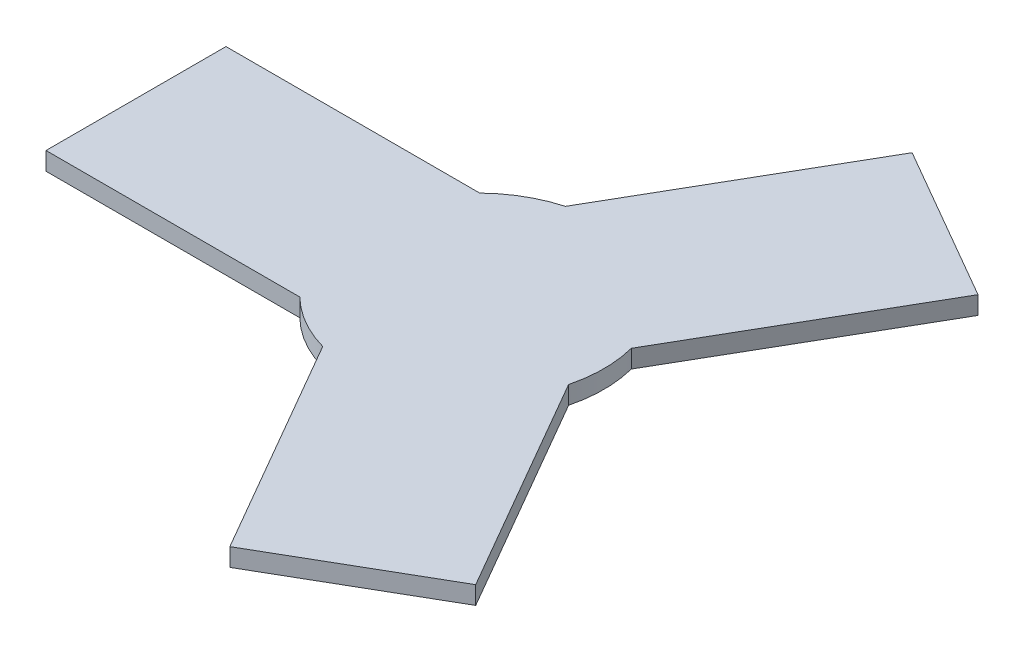
SolidWorks part; units mm, degrees
ref_plane "Plan de face" through (0, 0, 0) normal (0, 0, 1) x (1, 0, 0)
ref_plane "Plan de dessus" through (0, 0, 0) normal (0, 1, 0) x (1, 0, 0)
ref_plane "Plan de droite" through (0, 0, 0) normal (1, 0, 0) x (0, 0, -1)
sketch "Esquisse3" plane through (0, 0, 0) normal (0, 1, 0) x (1, 0, 0)
  line L0 (-150.1573, 0) -> (189.6273, 0) construction
  line L1 (-83.8395, -145.9242) -> (87.7229, 151.2306) construction
  line L2 (-78.0725, 135.2255) -> (117.7517, -203.9519) construction
  line L3 (-125, 131.2995) -> (-125, -153.5705) construction
  line L4 (-10.0538, -25) -> (-95, -25)
  line L5 (-10.0538, -25) -> (-10.0538, 25)
  line L6 (-10.0538, 25) -> (-14.4338, 25)
  line L7 (-95, -25) -> (-95, 25)
  line L8 (-10.0538, -25) -> (-95, 25) construction
  line L9 (-10.0538, 25) -> (-95, -25) construction
  line L10 (-24.4949, 25) -> (-95, 25)
  line L11 (33.8981, 8.7132) -> (69.1506, 69.7724)
  line L12 (25.8494, 94.7724) -> (69.1506, 69.7724)
  line L13 (-16.6237, 21.2069) -> (25.8494, 94.7724)
  line L14 (-9.4032, -33.7132) -> (25.8494, -94.7724)
  line L15 (69.1506, -69.7724) -> (25.8494, -94.7724)
  line L16 (26.6776, 3.7931) -> (69.1506, -69.7724)
  circle A0 centre (0, 0) radius 125
  circle A1 centre (0, 0) radius 35
  circle A2 centre (0, 0) radius 125
  circle A3 centre (0, 0) radius 125
  point P9 (-52.5269, 0)
  point P32 (0, 0)
  dimension "D1" = 250
  dimension "D4" = 70
  dimension "D2" = 120
  dimension "D3" = 120
  dimension "D5" = 30
  dimension "D6" = 50
  dimension "D7" = 84.9462
  dimension "D8" = 3
extrude "Boss.-Extru.3" add sketch "Esquisse3" along normal blind 5 contours A1 L13 L6 L5 L4 | A1 L10 L7 L4 | A1 L11 L12 L13 | L13 A1 L4 L5 L6 | A1 L14 L15 L16 region at (8.7965, 0, 0.5928) region at (-20.8738, 0, -1.4067) region at (-63.2967, 0, 0) region at (31.6483, 0, 54.8165) region at (31.6483, 0, -54.8165)
